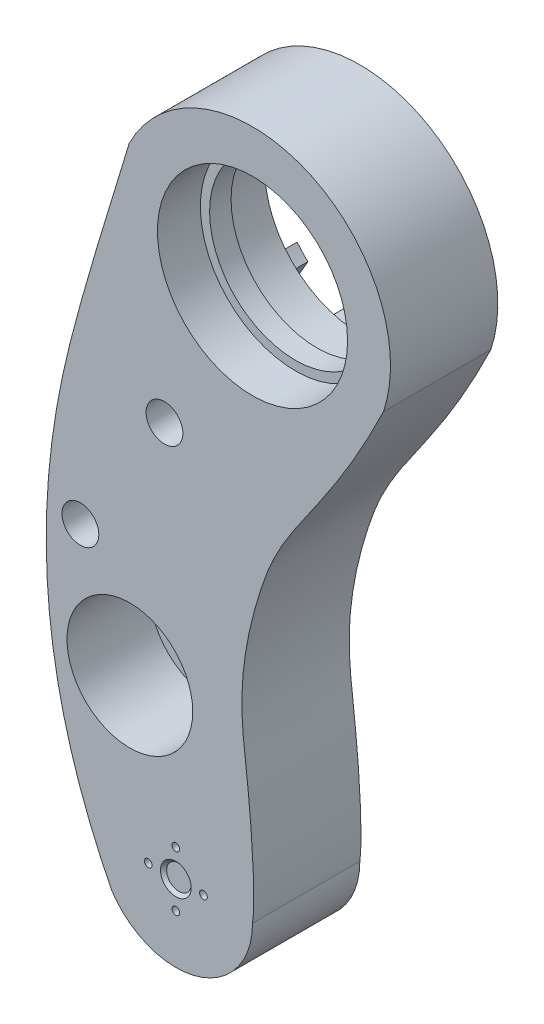
SolidWorks part; units mm, degrees
ref_plane "Ebene vorne" through (0, 0, 0) normal (0, 0, 1) x (1, 0, 0)
ref_plane "Ebene oben" through (0, 0, 0) normal (0, 1, 0) x (1, 0, 0)
ref_plane "Ebene rechts" through (0, 0, 0) normal (1, 0, 0) x (0, 0, -1)
sketch "Skizze1" plane through (0, 0, 0) normal (0, 0, 1) x (1, 0, 0)
  circle A0 centre (0, 0) radius 9
  circle A6 centre (0, 0) radius 25
  circle A7 centre (25, 180) radius 45
  circle A8 centre (25, 180) radius 28
  spline S0 degree 3 poles (-15.2208, 200.1813) (-29.5524, 153.6008) (-52.8158, 72.4942) (-36.5204, 17.1452) (-20.9233, -13.6827) knots 0 0 0 0 0.231856 1 1 1 1
  spline S1 degree 3 poles (67.7341, 165.9004) (51.1385, 131.5089) (36.2521, 119.622) (25.0061, 88.4676) (20.0361, 66.2697) (25.6637, 21.506) (25.7093, 4.904) (25, 0) knots 0 0 0 0 0.347734 0.409135 0.591244 0.652607 1 1 1 1
  point P3 (-37.8935, 141.1351)
  point P4 (-33.401, 138.4927)
  point P14 (0, 0)
  dimension "D1" = 18
  dimension "D3" = 50
  dimension "D5" = 90
  dimension "D7" = 56
  dimension "D4" = 180
  dimension "D6" = 25
extrude "Aufsatz-Linear austragen1" add sketch "Skizze1" along normal blind 35 contours S1 A7 S0 | S1 A7 S0 A6 | A6 S0 A0 | A0 region at (0, 0, 0) region at (-21.6749, -10.5823, 0) region at (-5.9767, 86.0945, 0) region at (8.8287, 139.373, 0)
sketch "Skizze2" plane through (0, 0, 35) normal (0, 0, 1) x (1, 0, 0)
  circle A0 centre (0, 0) radius 4
  dimension "D1" = 8
extrude "Schnitt-Linear austragen1" cut sketch "Skizze2" against normal blind 1 contours A0
chamfer "Fase1" distance 1 angle 45 1 edges at (4, 0, 35)
sketch "Skizze3" plane through (0, 0, 35) normal (0, 0, 1) x (1, 0, 0)
sketch "Skizze4" plane through (0, 0, 35) normal (0, 0, 1) x (1, 0, 0)
  arc A0 (-1.247, 8.9132) -> (-8.9132, 1.247) centre (0, 0) ccw
  circle A1 centre (9, 0) radius 1.25
  circle A2 centre (0, -9) radius 1.25
  circle A3 centre (-9, 0) radius 1.25
  circle A4 centre (0, 9) radius 1.25
  arc A5 (-8.9132, -1.247) -> (-1.247, -8.9132) centre (0, 0) ccw
  arc A6 (8.9132, 1.247) -> (1.247, 8.9132) centre (0, 0) ccw
  arc A7 (1.247, -8.9132) -> (8.9132, -1.247) centre (0, 0) ccw
  point P14 (0, 0)
  dimension "D1" = 18
  dimension "D2" = 4
  dimension "D3" = 2.5
extrude "Schnitt-Linear austragen2" cut sketch "Skizze4" against normal blind 15 contours A4 | A1 | A2 | A3 region at (0, 9, 35) region at (-9, 0, 35) region at (9, 0, 35) region at (0, -9, 35)
sketch "Skizze5" plane through (0, 0, 0) normal (0, 0, -1) x (-1, 0, 0)
  circle A0 centre (0, 0) radius 8
  circle A1 centre (8, 0) radius 1.25
  circle A2 centre (0, -8) radius 1.25
  circle A3 centre (-8, 0) radius 1.25
  circle A4 centre (0, 8) radius 1.25
  circle A5 centre (0, 0) radius 9.25
  point P14 (0, 0)
  dimension "D1" = 4
  dimension "D3" = 16
extrude "Schnitt-Linear austragen3" cut sketch "Skizze5" against normal blind 15 contours A0 A4 | A0 A4 | A0 A3 | A0 A3 | A0 A1 | A0 A1 | A0 A2 | A0 A2 region at (-7.4523, 0, 0) region at (-8.5125, 0, 0) region at (0, 7.4523, 0) region at (0, 8.5125, 0) region at (0, -8.5125, 0) region at (0, -7.4523, 0) region at (7.4523, 0, 0) region at (8.5125, 0, 0)
sketch "Skizze6" plane through (0, 0, 35) normal (0, 0, 1) x (1, 0, 0)
  line L0 (-40.7063, 50) -> (22.1206, 50) construction
  circle A1 centre (-15, 50) radius 12.5
  spline S0 degree 3 poles (-15.2208, 200.1813) (-29.5524, 153.6008) (-52.8158, 72.4942) (-36.5204, 17.1452) (-20.9233, -13.6827) knots 0 0 0 0 0.231856 1 1 1 1 construction
  spline S1 degree 3 poles (67.7341, 165.9004) (51.1385, 131.5089) (36.2521, 119.622) (25.0061, 88.4676) (20.0361, 66.2697) (25.6637, 21.506) (25.7093, 4.904) (25, 0) knots 0 0 0 0 0.347734 0.409135 0.591244 0.652607 1 1 1 1 construction
  dimension "D1" = 50
  dimension "D2" = 25
  dimension "D3" = 15
extrude "Schnitt-Linear austragen4" cut sketch "Skizze6" against normal blind 35
sketch "Skizze7" plane through (0, 0, 35) normal (0, 0, 1) x (1, 0, 0)
  circle A0 centre (-15, 50) radius 20.5
  dimension "D1" = 41
extrude "Schnitt-Linear austragen5" cut sketch "Skizze7" against normal offset from surface (27 mm away) 8 up to face at (-2.5, 50, 0)
sketch "Skizze8" plane through (0, 0, 8) normal (0, 0, 1) x (1, 0, 0)
  line L0 (-15, 50) -> (-13.8879, 32.5354) construction
  arc A0 (-18.0975, 67.2237) -> (-32.4775, 50.8878) centre (-15, 50) ccw
  circle A1 centre (-13.8879, 32.5354) radius 2
  circle A2 centre (-32.4646, 48.8879) radius 2
  circle A3 centre (-16.1121, 67.4646) radius 2
  circle A4 centre (2.4646, 51.1121) radius 2
  arc A5 (2.2237, 53.0975) -> (-14.1122, 67.4775) centre (-15, 50) ccw
  arc A6 (-11.9025, 32.7763) -> (2.2237, 53.0975) centre (-15, 50) ccw
  arc A7 (-32.4775, 50.8878) -> (-15.8878, 32.5225) centre (-15, 50) ccw
  point P14 (-15, 50)
  dimension "D1" = 4
  dimension "D2" = 4
  dimension "D3" = 17.5
extrude "Schnitt-Linear austragen6" cut sketch "Skizze8" against normal blind 15 contours A4 | A3 | A1 | A2 | A2 | A4 region at (-16.1121, 67.4646, 8) region at (-31.5973, 48.9431, 8) region at (1.5973, 51.0569, 8) region at (-13.8879, 32.5354, 8)
sketch "Skizze9" plane through (0, 0, 0) normal (0, 0, -1) x (-1, 0, 0)
  circle A0 centre (13.8879, 32.5354) radius 3.5
  circle A1 centre (-2.4646, 51.1121) radius 3.5
  circle A2 centre (16.1121, 67.4646) radius 3.5
  circle A3 centre (32.4646, 48.8879) radius 3.5
  point P3 (15, 50)
  point P14 (15, 50)
  dimension "D1" = 7
  dimension "D2" = 4
extrude "Schnitt-Linear austragen7" cut sketch "Skizze9" against normal blind 4
sketch "Skizze10" plane through (0, 0, 35) normal (0, 0, 1) x (1, 0, 0)
  circle A0 centre (25, 180) radius 31
  dimension "D1" = 62
extrude "Schnitt-Linear austragen8" cut sketch "Skizze10" against normal blind 14
ref_plane "Ebene1" through (0, 0, 17.5) normal (0, 0, 1) x (1, 0, 0)
mirror "Spiegeln1" about plane through (0, 0, 17.5) normal (0, 0, 1) of "Schnitt-Linear austragen8"
sketch "Skizze11" plane through (0, 0, 0) normal (0, 0, 1) x (1, 0, 0)
  circle A0 centre (12.8689, 101.3867) radius 1.65
extrude "Schnitt-Linear austragen10" cut sketch "Skizze11" along normal blind 15
sketch "Skizze12" plane through (0, 0, 0) normal (0, 0, -1) x (-1, 0, 0)
  line L1 (-2, 140) -> (-25, 180) construction
  circle A0 centre (-2, 140) radius 2.1
  circle A1 centre (-25, 180) radius 32
  circle A2 centre (-2, 140) radius 7.5
  circle A3 centre (-25, 180) radius 28 construction
  dimension "D1" = 4.2
  dimension "D2" = 15
  dimension "D3" = 64
  dimension "D4" = 40
  dimension "D5" = 23
extrude "Schnitt-Linear austragen11" cut sketch "Skizze12" against normal blind 15 contours A0 region at (2, 140, 0)
sketch "Sketch1" plane through (0, 0, 0) normal (0, 0, -1) x (-1, 0, 0)
  line L0 (-15.2142, 148.9382) -> (-8.0683, 136.5107)
  line L1 (-8.0683, 136.5107) -> (-15.5036, 149.4416) construction
  line L2 (-3.0775, 155.9168) -> (4.0522, 143.5173)
  line L3 (4.0683, 143.4893) -> (-3.3669, 156.4202) construction
  line L4 (4.0522, 143.5173) -> (0.4436, 159.6723)
  line L5 (-8.0683, 136.5107) -> (-20.8701, 147.6961)
  circle A0 centre (-25, 180) radius 32.5668
extrude "Boss-Extrude1" add sketch "Sketch1" along normal blind 5 contours A0 L5 L0 | A0 L2 L4 region at (14.6753, 144.3322, 0) region at (-0.4905, 152.988, 0)
sketch "Sketch2" plane through (0, 0, 0) normal (0, 0, -1) x (-1, 0, 0)
  circle A0 centre (3.7104, 126.9928) radius 6
extrude "Cut-Extrude1" cut sketch "Sketch2" against normal blind 35
ref_plane "Plane1" through (0, 0, 30) normal (0, 0, -1) x (-1, 0, 0)
sketch "Sketch3" plane through (0, 0, 17.5) normal (0, 0, -1) x (-1, 0, 0)
  line L0 (36.1621, 87.9577) -> (8.7453, 130.2563)
  line L1 (-1.3237, 123.7283) -> (26.1022, 81.4356)
  circle A1 centre (3.7104, 126.9928) radius 6
  circle A2 centre (31.1318, 84.6972) radius 5.9946
  point P9 (31.1318, 84.6972)
extrude "Cut-Extrude2" cut sketch "Sketch3" along normal blind 8 contours A2 L0 L1 | A2 region at (-17.421, 105.8452, 17.5) region at (-31.1318, 84.6972, 17.5)
sketch "Sketch4" plane through (0, 0, 35) normal (0, 0, 1) x (1, 0, 0)
  circle A0 centre (-31.1318, 84.6972) radius 6
  arc A1 (-36.1621, 87.9577) -> (-26.1022, 81.4356) centre (-31.1318, 84.6972) ccw construction
extrude "Cut-Extrude3" cut sketch "Sketch4" against normal up to surface (25.5 mm away) up to face at (-19.0525, 103.3286, 9.5)
sketch "Skizze13" plane through (0, 0, 0) normal (0, 0, -1) x (-1, 0, 0)
  circle A3 centre (-16.0818, 52.3597) radius 1.65
  circle A4 centre (-53.8461, 158.4958) radius 1.65
  circle A5 centre (4.4913, 200.5829) radius 1.65
extrude "Schnitt-Linear austragen12" cut sketch "Skizze13" against normal blind 15
